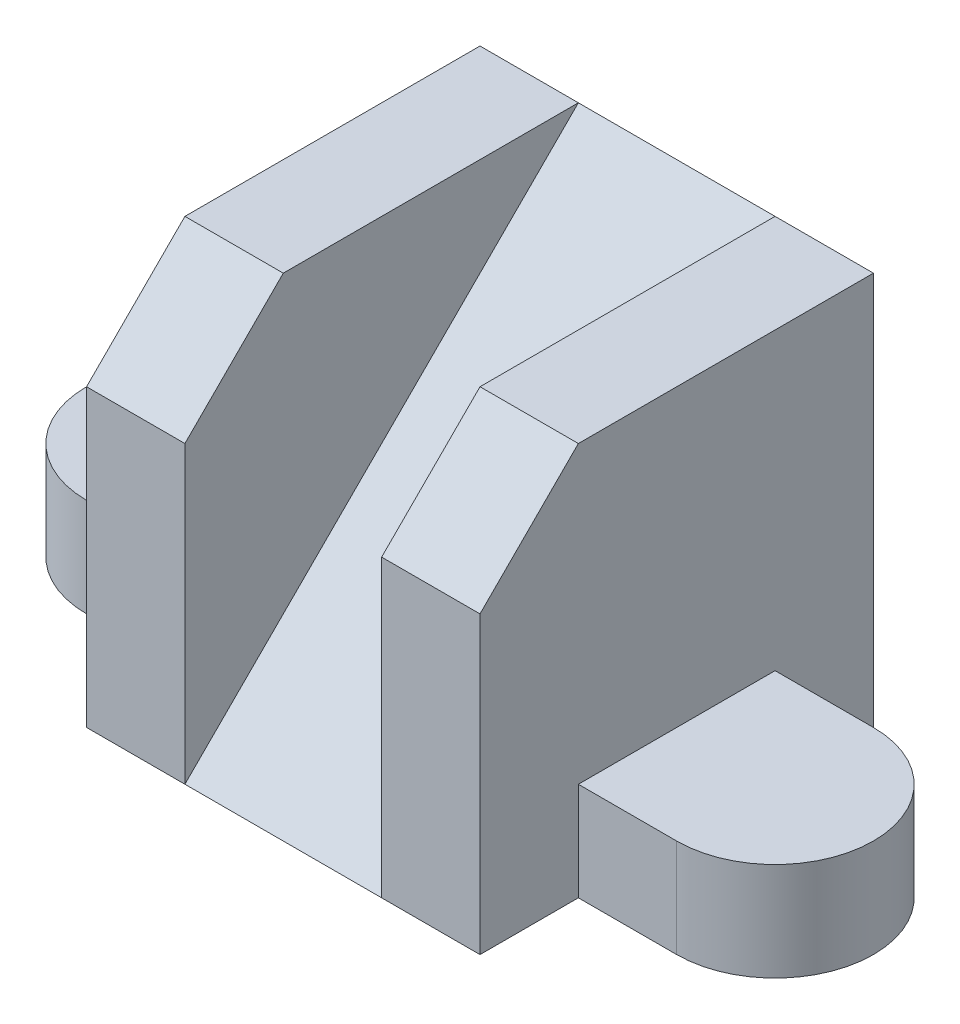
SolidWorks part; units mm, degrees
ref_plane "Front Plane" through (0, 0, 0) normal (0, 0, 1) x (1, 0, 0)
ref_plane "Top Plane" through (0, 0, 0) normal (0, 1, 0) x (1, 0, 0)
ref_plane "Right Plane" through (0, 0, 0) normal (1, 0, 0) x (0, 0, -1)
sketch "Sketch1" plane through (0, 0, 0) normal (0, 1, 0) x (1, 0, 0)
  line L0 (0, 14) -> (14, 14) construction
  line L1 (0, 0) -> (7, 0)
  line L2 (0, 0) -> (0, 28)
  line L3 (0, 28) -> (7, 28)
  line L4 (7, 0) -> (7, 28)
  line L5 (14, 21) -> (7, 21)
  line L6 (14, 7) -> (7, 7)
  arc A0 (14, 7) -> (14, 21) centre (14, 14) ccw
  dimension "D3" = 14
  dimension "D1" = 7
  dimension "D2" = 28
  dimension "D4" = 14
extrude "Boss-Extrude1" add sketch "Sketch1" along normal blind 28 contours L2 L0 L4 L3 | L0 L2 L1 L4 region at (3.5, 0, -21) region at (3.5, 0, -7)
extrude "Boss-Extrude2" add sketch "Sketch1<3>" along normal blind 7 contours L6 A0 L5 L4 region at (13.3466, 0, -14)
sketch "Sketch1<3>" plane through (0, 0, 0) normal (0, 1, 0) x (1, 0, 0) same geometry as "Sketch1"
chamfer "Chamfer1" distance 7 1 edges at (3.5, 28, 0)
sketch "Sketch2" plane through (0, 0, 0) normal (-1, 0, 0) x (0, 0, 1)
  line L0 (-28, 28) -> (0, 0)
  line L5 (0, 0) -> (0, 21)
  line L6 (0, 21) -> (-7, 28)
  line L7 (-7, 28) -> (-28, 28)
  line L8 (-28, 28) -> (-28, 0)
  line L9 (-28, 0) -> (0, 0)
  line L13 (-28, 28) -> (-28, 0)
  line L14 (-28, 0) -> (0, 0)
  dimension "D1" = 0
extrude "Boss-Extrude3" add sketch "Sketch2" along normal blind 7
mirror "Mirror1" about plane through (-7, 0, 0) normal (1, 0, 0) of bodies 103
